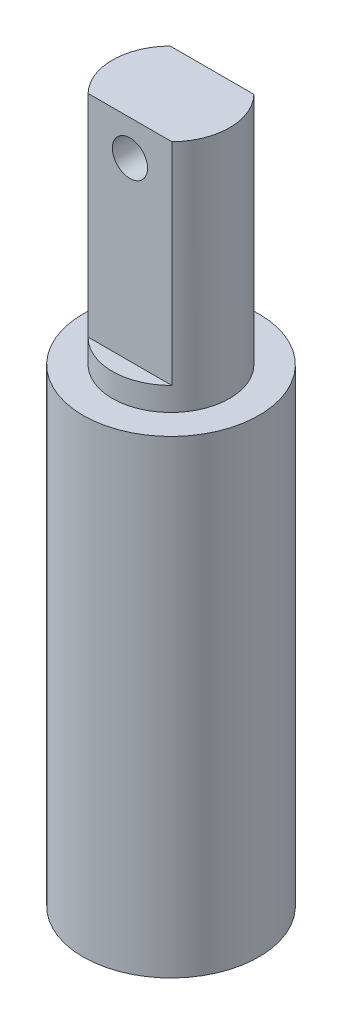
SolidWorks part; units mm, degrees
ref_plane "Płaszczyzna przednia" through (0, 0, 0) normal (0, 0, 1) x (1, 0, 0)
ref_plane "Płaszczyzna górna" through (0, 0, 0) normal (0, 1, 0) x (1, 0, 0)
ref_plane "Płaszczyzna prawa" through (0, 0, 0) normal (1, 0, 0) x (0, 0, -1)
sketch "Szkic1" plane through (0, 0, 0) normal (0, 1, 0) x (1, 0, 0)
  circle A0 centre (0, 0) radius 5
  circle A1 centre (0, 0) radius 7.5
  dimension "D1" = 10
  dimension "D2" = 15
extrude "Dodanie-wyciągnięcie1" add sketch "Szkic1" along normal blind 40
extrude "Dodanie-wyciągnięcie2" add sketch "Szkic1<2>" along normal blind 50 from offset 10 contours A0 region at (0, 0, 0)
sketch "Szkic1<2>" plane through (0, 0, 0) normal (0, 1, 0) x (1, 0, 0) same geometry as "Szkic1"
sketch "Szkic2" plane through (0, 60, 0) normal (0, 1, 0) x (1, 0, 0)
  line L1 (5, -3.5) -> (-5, -3.5)
  line L2 (5, -3.5) -> (5, 3.5)
  line L3 (5, 3.5) -> (-5, 3.5)
  line L4 (-5, -3.5) -> (-5, 3.5)
  line L5 (5, -3.5) -> (-5, 3.5) construction
  line L6 (5, 3.5) -> (-5, -3.5) construction
  circle A0 centre (0, 0) radius 5 construction
  point P0 (0, 0)
  dimension "D1" = 7
extrude "Wytnij-wyciągnięcie1" cut sketch "Szkic2" against normal blind 18 flip side to cut
sketch "Szkic3" plane through (0, 0, 3.5) normal (0, 0, 1) x (1, 0, 0)
  line L0 (-3.5707, 60) -> (3.5707, 60) construction
  circle A0 centre (0, 57) radius 1.5
  dimension "D1" = 3
  dimension "D2" = 3
extrude "Wytnij-wyciągnięcie2" cut sketch "Szkic3" against normal blind 10
